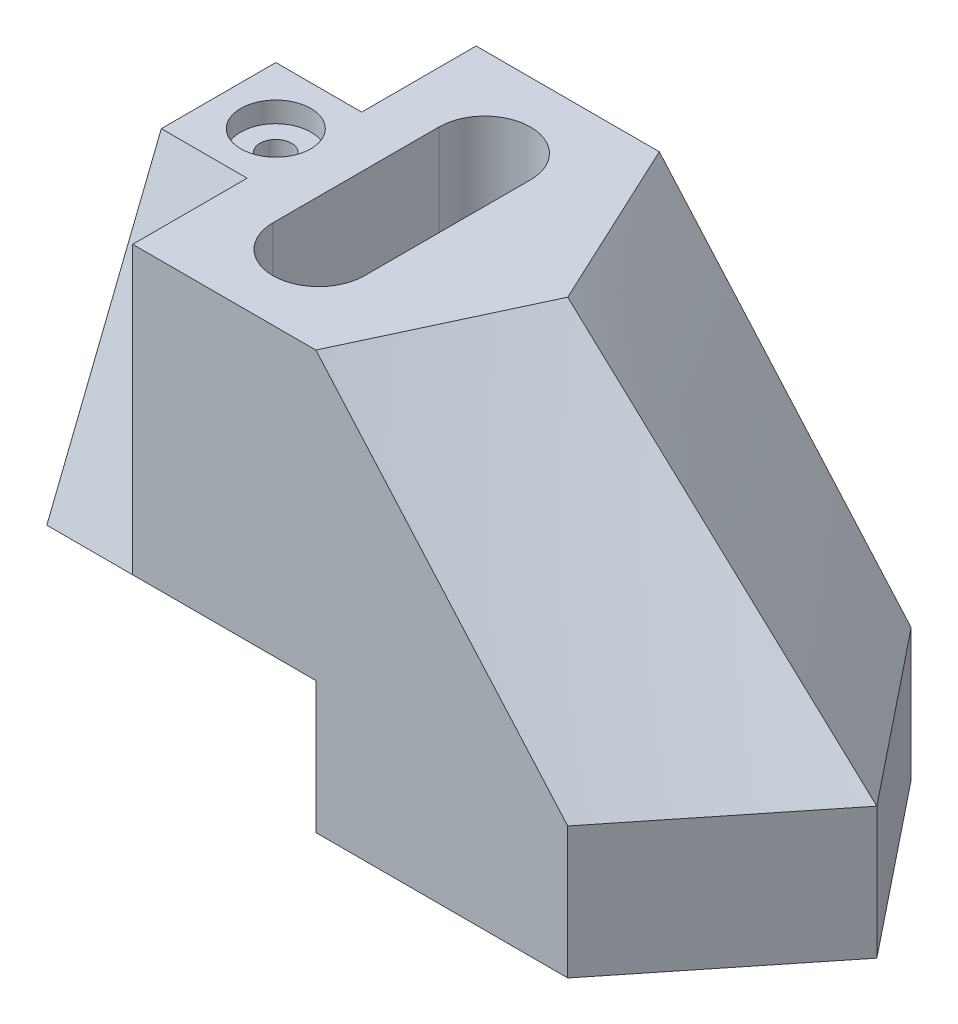
SolidWorks part; units mm, degrees
material "Titanium"
ref_plane "Front Plane" through (0, 0, 0) normal (0, 0, 1) x (1, 0, 0)
ref_plane "Top Plane" through (0, 0, 0) normal (0, 1, 0) x (1, 0, 0)
ref_plane "Right Plane" through (0, 0, 0) normal (1, 0, 0) x (0, 0, -1)
sketch "Sketch1" plane through (0, 0, 0) normal (0, 1, 0) x (1, 0, 0)
  line L0 (0, 0) -> (124.3028, 0) construction
  line L1 (0, -30) -> (0, 30)
  line L2 (0, 30) -> (91, 30)
  line L3 (0, -30) -> (91, -30)
  line L4 (91, 30) -> (115, 0)
  line L5 (91, -30) -> (115, 0)
  dimension "D1" = 60
  dimension "D2" = 91
  dimension "D3" = 115
ref_plane "Plane3" through (0, 50, 0) normal (0, 1, 0) x (1, 0, 0)
sketch "Sketch15" plane through (0, 50, 0) normal (0, 1, 0) x (1, 0, 0)
  line L0 (0, 30) -> (0, -30)
  line L1 (0, -30) -> (47, -30)
  line L2 (0, -30) -> (91, -30) construction
  line L3 (47, -30) -> (61, 0)
  line L4 (0, 0) -> (124.3028, 0) construction
  line L5 (61, 0) -> (47, 30)
  line L6 (0, 30) -> (91, 30) construction
  line L7 (47, 30) -> (0, 30)
  dimension "D1" = 47
  dimension "D2" = 61
loft "Loft2" add profiles "Sketch15", "Sketch1" connector at (0, 50, -30) connector at (0, 0, -30)
sketch "Sketch16" plane through (0, 0, 0) normal (0, -1, 0) x (1, 0, 0)
  line L5 (91, 30) -> (0, 30)
  line L6 (0, 30) -> (0, -30)
  line L7 (0, -30) -> (91, -30)
  line L8 (91, -30) -> (115, 0)
  line L9 (115, 0) -> (91, 30)
  line L10 (91, 30) -> (0, 30)
  line L11 (0, 30) -> (0, -30)
  line L12 (0, -30) -> (91, -30)
  line L13 (91, -30) -> (115, 0)
  line L14 (115, 0) -> (91, 30)
  dimension "D1" = 0
extrude "Boss-Extrude2" add sketch "Sketch16" along normal blind 23
sketch "Sketch17" plane through (0, 0, 30) normal (0, 0, 1) x (1, 0, 0)
  line L0 (91, -23) -> (0, -23) construction
  line L1 (0, 0) -> (47, 0)
  line L2 (0, 0) -> (0, -23)
  line L3 (0, -23) -> (47, -23)
  line L4 (47, 0) -> (47, -23)
  dimension "D1" = 47
extrude "Cut-Extrude5" cut sketch "Sketch17" against normal through all
sketch "Sketch19" plane through (0, 0, 0) normal (-1, 0, 0) x (0, 0, 1)
  line L0 (0, 0) -> (0, 50) construction
  line L1 (-30, 50) -> (30, 50) construction
  line L2 (10, 50) -> (30, 50)
  line L3 (-10, 50) -> (-30, 50)
  line L4 (30, 50) -> (30, 0)
  line L5 (-30, 50) -> (-30, 0)
  line L6 (30, 0) -> (10, 50)
  line L7 (-30, 0) -> (-10, 50)
  dimension "D1" = 20
extrude "Cut-Extrude6" cut sketch "Sketch19" against normal blind 15
sketch "Sketch20" plane through (0, 50, 0) normal (0, 1, 0) x (1, 0, 0)
  line L0 (32, 14.5) -> (32, -14.5) construction
  line L1 (35, 14.5) -> (35, -14.5)
  line L2 (29, 14.5) -> (29, -14.5)
  line L3 (32, 0) -> (0, 0) construction
  line L4 (0, 10) -> (0, -10) construction
  line L5 (40, 14.5) -> (40, -14.5)
  line L6 (24, 14.5) -> (24, -14.5)
  arc A0 (35, 14.5) -> (29, 14.5) centre (32, 14.5) ccw
  arc A1 (29, -14.5) -> (35, -14.5) centre (32, -14.5) ccw
  arc A2 (24, -14.5) -> (40, -14.5) centre (32, -14.5) ccw
  arc A3 (40, 14.5) -> (24, 14.5) centre (32, 14.5) ccw
  point P2 (32, 0)
  dimension "D1" = 3
  dimension "D2" = 35
  dimension "D3" = 32
  dimension "D4" = 5
extrude "Cut-Extrude7" cut sketch "Sketch20" against normal blind 20
extrude "Cut-Extrude8" cut sketch "Sketch20<2>" against normal through all contours L2 A1 L1 A0 region at (32, 50, 0)
sketch "Sketch20<2>" plane through (0, 50, 0) normal (0, 1, 0) x (1, 0, 0) same geometry as "Sketch20"
hole_wizard "CBORE for M5 Hex Head Bolt2" positions "Sketch22" profile "Sketch23" counterbore size "M5" standard "ANSI Metric" end condition through all
sketch "Sketch22" plane through (0, 50, 0) normal (0, 1, 0) x (1, 0, 0)
  line L0 (0, 10) -> (0, -10) construction
  line L1 (15, -10) -> (0, -10) construction
  point P0 (10, 0)
  dimension "D1" = 10
  dimension "D2" = 10
sketch "Sketch23" plane through (10, 50, 0) normal (1, 0, 0) x (0, 0, 1)
  line L0 (0, 0) -> (0, 73)
  line L1 (0, 73) -> (2.75, 73)
  line L3 (2.75, 73) -> (2.75, 3.58)
  line L4 (2.75, 3.58) -> (6.12, 3.58)
  line L5 (6.12, 3.58) -> (6.12, 0)
  line L7 (6.12, 0) -> (0, 0)
  line L11 (0, -6.35) -> (0, 107.95) construction
  dimension "Thru Hole Dia." = 5.5
  dimension "Thru Hole Depth" = 73
  dimension "C'Bore Dia." = 12.24
  dimension "C'Bore Depth" = 3.58
